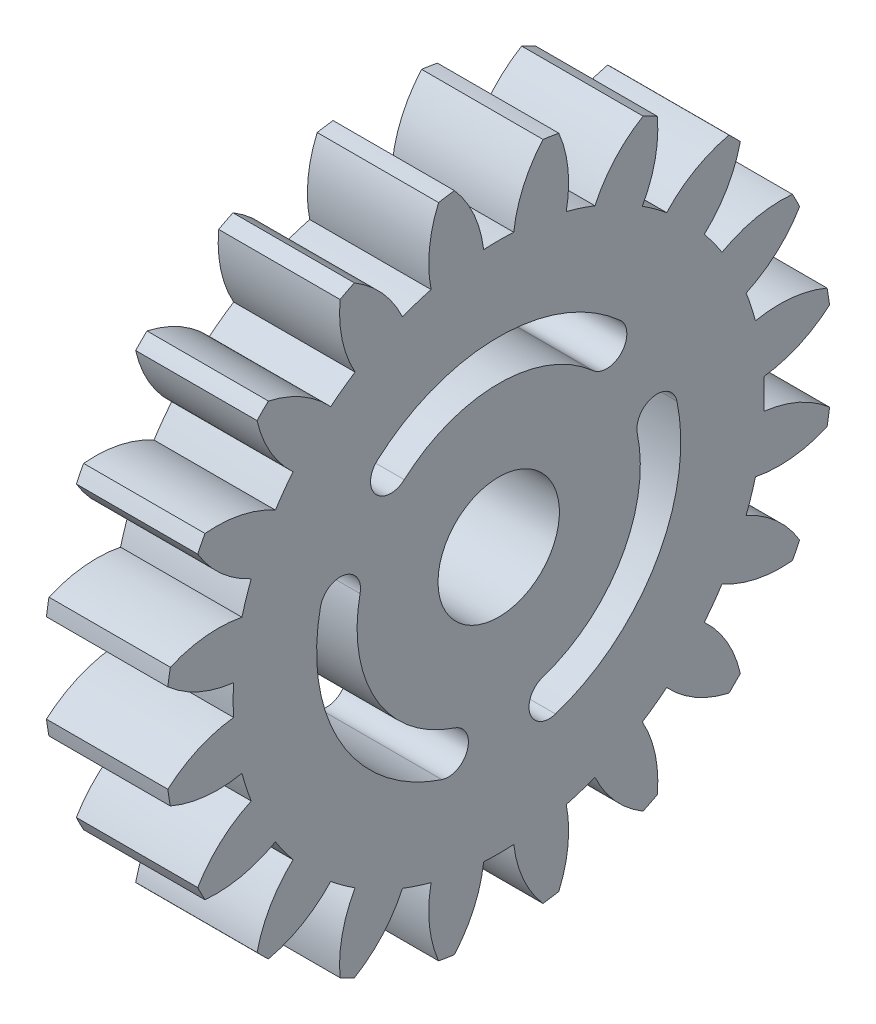
SolidWorks part; units mm, degrees
ref_plane "Plane1" through (0, 0, 0) normal (0, 0, 1) x (1, 0, 0)
ref_plane "Plane2" through (0, 0, 0) normal (0, 1, 0) x (1, 0, 0)
ref_plane "Plane3" through (0, 0, 0) normal (1, 0, 0) x (0, 0, -1)
sketch "HoldingSke" plane through (0, 0, 0) normal (0, 1, 0) x (1, 0, 0)
  line L0 (0, 0) -> (0.6265, -0.228)
  line L1 (-15, 0) -> (100, 0) construction
  line L2 (0, 0) -> (-2.1039, 2.3779)
  line L3 (0, 0) -> (-11.863, 4.5341)
  line L4 (0, 0) -> (8.1152, 2.9537)
  line L5 (0, 0) -> (-46.8476, -17.4728)
  line L6 (0, 0) -> (-4.9738, -3.3558)
  line L7 (-2.1039, 2.3779) -> (8.6586, 51.2059)
  line L8 (-76.2, 54.61) -> (-75.2, 54.61)
  line L9 (-71.009, 38.7566) -> (-53.1078, 45.2721)
  line L10 (-76.2, 71.12) -> (104.1128, 71.12)
  line L11 (0, 0) -> (-6, 0)
  line L12 (-76.2, 101.6) -> (-76.147, 101.6)
  line L13 (24.9733, 27.94) -> (52.9518, 28.4284)
  line L14 (24.9733, 27.94) -> (24.9743, 27.94)
  line L15 (24.9733, 27.94) -> (100.4006, 29.5858)
  line L16 (-63.627, -1.5) -> (-12.827, -1.5)
  circle A0 centre (0, 0) radius 3
  circle A1 centre (0, 0) radius 13.124
  circle A2 centre (0, 0) radius 37.5
  circle A3 centre (0, 0) radius 3
  dimension "Num_teeth" = 20
  dimension "Pitch_radius" = 180.3128
  dimension "Width" = 6
  dimension "Thickness" = 6
sketch "BasProSke" plane through (0, 0, 0) normal (0, 1, 0) x (1, 0, 0)
  line L0 (-10, 0) -> (60, 0) construction
  line L1 (0, 0) -> (0, 16.5)
  line L2 (0, 0) -> (6, 0)
  line L3 (6, 0) -> (6, 16.5)
  line L4 (6, 16.5) -> (0, 16.5)
  dimension "Thickness" = 6
  dimension "Diameter" = 33
revolve "Base-Revolve" add sketch "BasProSke" angle 360 about L0
sketch "TooCutSke" plane through (0, 0, 0) normal (1, 0, 0) x (0, 0, -1)
  line L1 (0, 0) -> (0, 107) construction
  line L2 (0, 0) -> (-1.2696, 14.9462) construction
  line L3 (0, 0) -> (-4.6808, 29.5532) construction
  line L4 (-1.2696, 14.9462) -> (-2.3404, 14.7766) construction
  arc A0 (0.7438, 13.1029) -> (-0.7438, 13.1029) centre (0, 0) ccw
  arc A1 (2.21, 16.377) -> (-2.21, 16.377) centre (0, 0) ccw
  circle A2 centre (0, 0) radius 15 construction
  circle A3 centre (0, 0) radius 14.0954 construction
  arc A4 (-0.7438, 13.1029) -> (-2.21, 16.377) centre (-6.7025, 12.3999) ccw
  arc A5 (2.21, 16.377) -> (0.7438, 13.1029) centre (6.7025, 12.3999) ccw
extrude "ToothCut" cut sketch "TooCutSke" along normal through all
fillet "Breaks" [suppressed] radius 0.03 tangent propagation no
fillet "RootFillets" [suppressed] radius 0.376
pattern_circular "TeethCuts" count 20 every 18 about axis through (-10, 0, 0) along (1, 0, 0) of "ToothCut", "RootFillets", "Breaks"
sketch "HubNeaOneSke" plane through (0, 0, 0) normal (-1, 0, 0) x (0, 0, 1)
  circle A0 centre (0, 0) radius 13.124
  dimension "Diameter" = 26.248
extrude "HubNearOne" [suppressed] add sketch "HubNeaOneSke" along normal blind 44.0001
sketch "HubNeaBotSke" plane through (0, 0, 0) normal (-1, 0, 0) x (0, 0, 1)
  circle A0 centre (0, 0) radius 13.124
  dimension "Diameter" = 26.248
extrude "HubNearBoth" [suppressed] add sketch "HubNeaBotSke" along normal blind 22
ref_plane "FarPln" through (6, 0, 0) normal (1, 0, 0) x (0, 0, -1)
sketch "HubFarSke" plane through (6, 0, 0) normal (1, 0, 0) x (0, 0, -1)
  circle A0 centre (0, 0) radius 13.124
  dimension "Diameter" = 26.248
extrude "HubFar" [suppressed] add sketch "HubFarSke" along normal blind 22
sketch "BorSke" plane through (0, 0, 0) normal (1, 0, 0) x (0, 0, -1)
  circle A0 centre (0, 0) radius 3
  dimension "Diameter" = 6
extrude "Bore" cut sketch "BorSke" along normal mid plane 100.0001
sketch "KeySke" plane through (0, 0, 0) normal (1, 0, 0) x (0, 0, -1)
  line L0 (-1, 0) -> (-1, 4)
  line L1 (-1, 4) -> (1, 4)
  line L2 (1, 4) -> (1, 0)
  line L3 (0, 0) -> (0, 34) construction
  line L4 (-1, 0) -> (1, 0)
  dimension "Width" = 2
extrude "Keyway" [suppressed] cut sketch "KeySke" along normal mid plane 100.0001
pattern_circular "Keyway2" [suppressed] count 2 every 90 about axis through (-10, 0, 0) along (1, 0, 0) reverse direction yes
sketch "Sketch1" plane through (6, 0, 0) normal (1, 0, 0) x (0, 0, -1)
  line L0 (6, 6.7082) -> (4.6667, 5.2175) construction
  line L1 (0, 0) -> (0, 14.2294) construction
  arc A0 (0, 9) -> (6, 6.7082) centre (0, 0) cw
  arc A1 (0, 7) -> (4.6667, 5.2175) centre (0, 0) cw
  circle A2 centre (5.3333, 5.9628) radius 1
  arc A3 (0, 7) -> (-4.6667, 5.2175) centre (0, 0) ccw
  arc A4 (0, 9) -> (-6, 6.7082) centre (0, 0) ccw
  circle A5 centre (-5.3333, 5.9628) radius 1
  dimension "D1" = 9
  dimension "D3" = 6
  dimension "D2" = 2
extrude "Cut-Extrude1" cut sketch "Sketch1" against normal blind 10 contours A4 A5 A3 A1 A2 A0 | A5 | A2 region at (6, 7.5179, 0) region at (6, 5.9628, -5.3333) region at (6, 5.9628, 5.3333)
pattern_circular "CirPattern1" count 3 over 360 about axis through (6, 0, 0) along (1, 0, 0) of "Cut-Extrude1"
equation "' \"Module@HoldingSke\" = 6.35"
equation "' \"Num_teeth@HoldingSke\" = 12"
equation "' \"Ap@HoldingSke\" =  20"
equation "' \"Ap@HoldingSke\" = 20"
equation "' \"Width@HoldingSke\" = 0.5 * 25.4"
equation "' \"Hub_dia@HoldingSke\"= 1 * 25.4"
equation "' \"Hub_dia@HoldingSke\" = 1 * 25.4"
equation "' \"Overall_len@HoldingSke\" = 1.0 * 25.4"
equation "' \"Bore@HoldingSke\" = 0.75 * 25.4"
equation "' \"T_dim@HoldingSke\" = 0.1 * 25.4"
equation "' \"Width@KeySke\" = 0.25 * 25.4"
equation "' \"Show_teeth@HoldingSke\" = 13"
equation "' \"Backlash@HoldingSke\" = 0.009 * 25.4"
equation "' \"Addendum_fac@HoldingSke\" = 1.0"
equation "' \"Dedendum_fac@HoldingSke\" = 1.25"
equation "' \"Dedendum_add@HoldingSke\" = 0.00005 * 25.4"
equation "' \"Clearance_fac@HoldingSke\" = 0.25"
equation "\"Pitch@HoldingSke\" = 1 / \"Module@HoldingSke\""
equation "\"Overcut_dia@TooCutSke\" = (\"Num_teeth@HoldingSke\" + 2 * \"Addendum_fac@HoldingSke\") / \"Pitch@HoldingSke\" + 0.002 * 25.4"
equation "\"Pitch_dia@TooCutSke\" = \"Num_teeth@HoldingSke\" / \"Pitch@HoldingSke\""
equation "\"Base_dia@TooCutSke\" = \"Num_teeth@HoldingSke\" / \"Pitch@HoldingSke\" * cos((\"Ap@HoldingSke\"  * 3.14159265 / 180))"
equation "\"Root_dia@TooCutSke\" = (\"Num_teeth@HoldingSke\" + 2) / \"Pitch@HoldingSke\" - 2 * (\"Addendum_fac@HoldingSke\" + \"Dedendum_fac@HoldingSke\") / \"Pitch@HoldingSke\" - \"Dedendum_add@HoldingSke\" * 2"
equation "\"Half_ang@TooCutSke\" = 180 / \"Num_teeth@HoldingSke\""
equation "\"Half_CT@TooCutSke\" = \"Num_teeth@HoldingSke\" / \"Pitch@HoldingSke\" * sin((3.14159265 / 2 / \"Num_teeth@HoldingSke\")) / 2 - 7 * \"Backlash@HoldingSke\" / 4"
equation "\"Flank_rad@TooCutSke\" = \"Num_teeth@HoldingSke\" / \"Pitch@HoldingSke\" / 5"
equation "\"Radius@RootFillets\" = \"Clearance_fac@HoldingSke\" / \"Pitch@HoldingSke\" + \"Dedendum_add@HoldingSke\""
equation "\"Break_rad@Breaks\" = 0.02 / \"Pitch@HoldingSke\""
equation "\"Thickness@HoldingSke\" = \"Width@HoldingSke\""
equation "\"OAL@HoldingSke\" = \"Thickness@HoldingSke\""
equation "\"MHD@HoldingSke\" = (\"Num_teeth@HoldingSke\" + 2) / \"Pitch@HoldingSke\" - 2 * (\"Addendum_fac@HoldingSke\" + \"Dedendum_fac@HoldingSke\")  / \"Pitch@HoldingSke\" - \"Dedendum_add@HoldingSke\" * 2"
equation "\"MBD@HoldingSke\" = (\"Num_teeth@HoldingSke\" + 2) / \"Pitch@HoldingSke\" - 2 * (\"Addendum_fac@HoldingSke\" + \"Dedendum_fac@HoldingSke\")  / \"Pitch@HoldingSke\" - \"Dedendum_add@HoldingSke\" * 2 - 0.002 * 25.4"
equation "\"MHD@HoldingSke\" = ((sgn( \"MHD@HoldingSke\" - \"Hub_dia@HoldingSke\" )-1)*( \"MHD@HoldingSke\" - \"Hub_dia@HoldingSke\" ))/-2+ \"Hub_dia@HoldingSke\""
equation "\"MBD@HoldingSke\" = ((sgn( \"MBD@HoldingSke\" - \"Bore@HoldingSke\" )-1)*( \"MBD@HoldingSke\" - \"Bore@HoldingSke\" ))/-2+ \"Bore@HoldingSke\""
equation "\"OAL@HoldingSke\" = ((sgn( \"OAL@HoldingSke\" - \"Overall_len@HoldingSke\" )+1)*( \"OAL@HoldingSke\" - \"Overall_len@HoldingSke\" ))/2 + \"Overall_len@HoldingSke\" + 0.000002 * 25.4"
equation "\"Num_teeth@TeethCuts\" = int( \"Show_teeth@HoldingSke\" ) + 1"
equation "\"Num_teeth@TeethCuts\" = ((sgn( \"Num_teeth@TeethCuts\" - \"Num_teeth@HoldingSke\" )-1)*( \"Num_teeth@TeethCuts\" - \"Num_teeth@HoldingSke\" ))/-2+ \"Num_teeth@HoldingSke\""
equation "\"Num_teeth@TeethCuts\" = ((sgn( \"Num_teeth@TeethCuts\" - 2.0)+1)*( \"Num_teeth@TeethCuts\" - 2.0))/2 +2.0"
equation "\"Angle@TeethCuts\" = 360.0 / \"Num_teeth@HoldingSke\""
equation "\"Diameter@BasProSke\" = (\"Num_teeth@HoldingSke\" + 2 * \"Addendum_fac@HoldingSke\") / \"Pitch@HoldingSke\""
equation "\"Thickness@BasProSke\"  = \"Thickness@HoldingSke\""
equation "' \"Fillet_rad@BasProSke\" =  \"Thickness@HoldingSke\" * 0.05"
equation "' \"Fillet_rad@BasProSke\" = \"Thickness@HoldingSke\" * 0.05"
equation "\"MHD@HoldingSke\" = ((sgn( \"MHD@HoldingSke\" - \"Root_dia@TooCutSke\" )-1)*( \"MHD@HoldingSke\" - \"Root_dia@TooCutSke\" ))/-2+ \"Root_dia@TooCutSke\""
equation "\"Diameter@HubNeaOneSke\" = \"MHD@HoldingSke\""
equation "\"Length@HubNearOne\" = \"OAL@HoldingSke\" - \"Thickness@BasProSke\""
equation "\"Diameter@HubNeaBotSke\" = \"MHD@HoldingSke\""
equation "\"Length@HubNearBoth\" = ( \"OAL@HoldingSke\" - \"Thickness@BasProSke\" ) / 2.0"
equation "\"Thickness@FarPln\" = \"Thickness@BasProSke\""
equation "\"Diameter@HubFarSke\" = \"MHD@HoldingSke\""
equation "\"Length@HubFar\" = ( \"OAL@HoldingSke\" - \"Thickness@BasProSke\" ) / 2.0"
equation "\"Diameter@BorSke\" = \"MBD@HoldingSke\""
equation "\"D1@Bore\" = \"OAL@HoldingSke\" * 2.0"
equation "\"D1@Keyway\" = \"OAL@HoldingSke\" * 2.0"
equation "\"Offset@KeySke\" = \"T_dim@HoldingSke\" + \"MBD@HoldingSke\" / 2.0"
